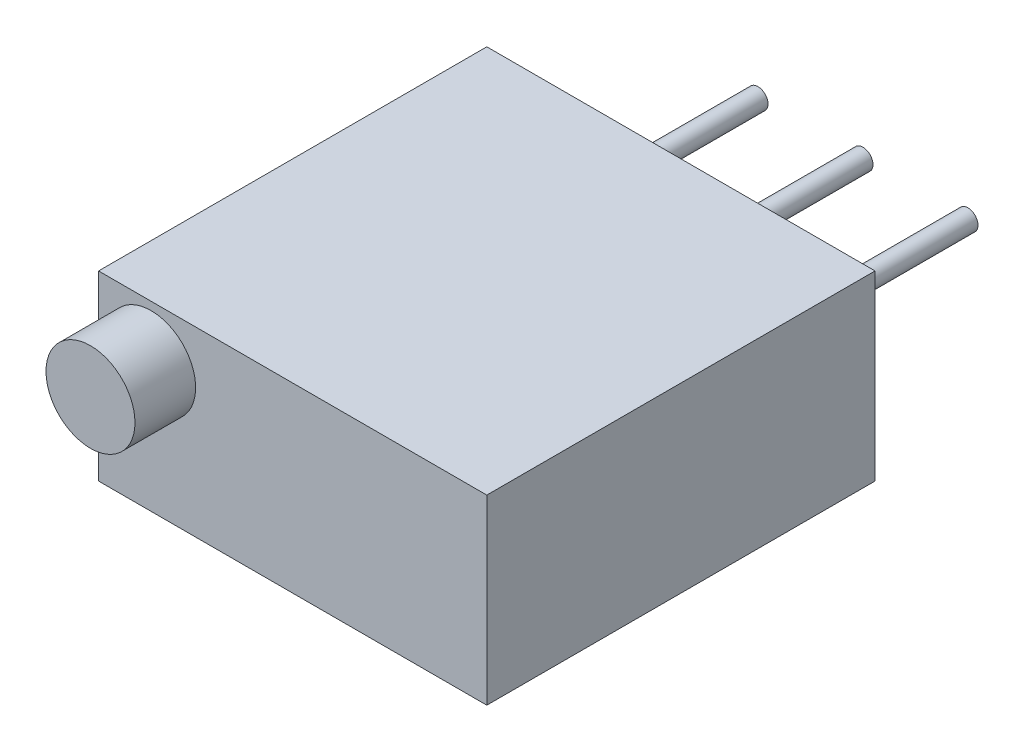
SolidWorks part; units mm, degrees
ref_plane "前视" through (0, 0, 0) normal (0, 0, 1) x (1, 0, 0)
ref_plane "上视" through (0, 0, 0) normal (0, 1, 0) x (1, 0, 0)
ref_plane "右视" through (0, 0, 0) normal (1, 0, 0) x (0, 0, -1)
sketch "草图1" plane through (0, 0, 0) normal (0, 1, 0) x (1, 0, 0)
  line L0 (0, 81.3418) -> (0, -101.3275) construction
  line L1 (-87.3375, 0) -> (113.7186, 0) construction
  line L3 (-4.8, 4.8) -> (4.8, 4.8)
  line L4 (-4.8, 4.8) -> (-4.8, -4.8)
  line L5 (-4.8, -4.8) -> (4.8, -4.8)
  line L6 (4.8, 4.8) -> (4.8, -4.8)
  dimension "D1" = 9.6
  dimension "D2" = 9.6
extrude "拉伸1" add sketch "草图1" along normal blind 4.5
sketch "草图3" plane through (0, 0, -4.8) normal (0, 0, -1) x (-1, 0, 0)
  line L0 (-5.1663, 2.25) -> (6.6013, 2.25) construction
  line L2 (0, 5.9307) -> (0, -2.165) construction
  circle A0 centre (0, 2.25) radius 0.25
  circle A1 centre (2.596, 2.25) radius 0.25
  circle A2 centre (-2.596, 2.25) radius 0.25
  dimension "D1" = 0.5
extrude "拉伸3" add sketch "草图3" along normal blind 4.5
sketch "草图4" plane through (0, 0, 4.8) normal (0, 0, 1) x (1, 0, 0)
  line L0 (-4.8, 3.2) -> (-3.5, 3.2)
  line L1 (-4.8, 4.5) -> (-4.8, 0) construction
  circle A0 centre (-3.5, 3.2) radius 1.1
  dimension "D3" = 2.2
  dimension "D1" = 1.3
  dimension "D2" = 1.3
extrude "凸台-拉伸1" add sketch "草图4" along normal blind 1.5 contours A0 region at (-3.5, 2.1311, 4.8)
